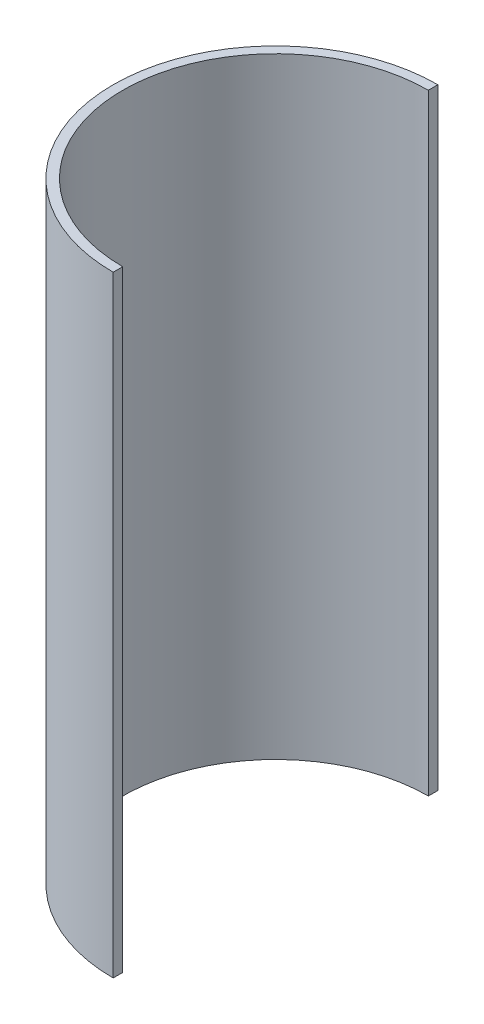
SolidWorks part; units mm, degrees
ref_plane "Front Plane" through (0, 0, 0) normal (0, 0, 1) x (1, 0, 0)
ref_plane "Top Plane" through (0, 0, 0) normal (0, 1, 0) x (1, 0, 0)
ref_plane "Right Plane" through (0, 0, 0) normal (1, 0, 0) x (0, 0, -1)
sketch "Sketch1" plane through (0, 0, 0) normal (0, 1, 0) x (1, 0, 0)
  line L1 (0, 107.95) -> (0, 101.6)
  line L2 (0, -101.6) -> (0, -107.95)
  arc A1 (0, 101.6) -> (0, -101.6) centre (0, 0) ccw
  arc A2 (0, 107.95) -> (0, -107.95) centre (0, 0) ccw
  dimension "D1" = 101.6
  dimension "D2" = 6.35
  dimension "D3" = 107.95
  dimension "D4" = 6.35
extrude "Boss-Extrude1" add sketch "Sketch1" along normal blind 406.4
